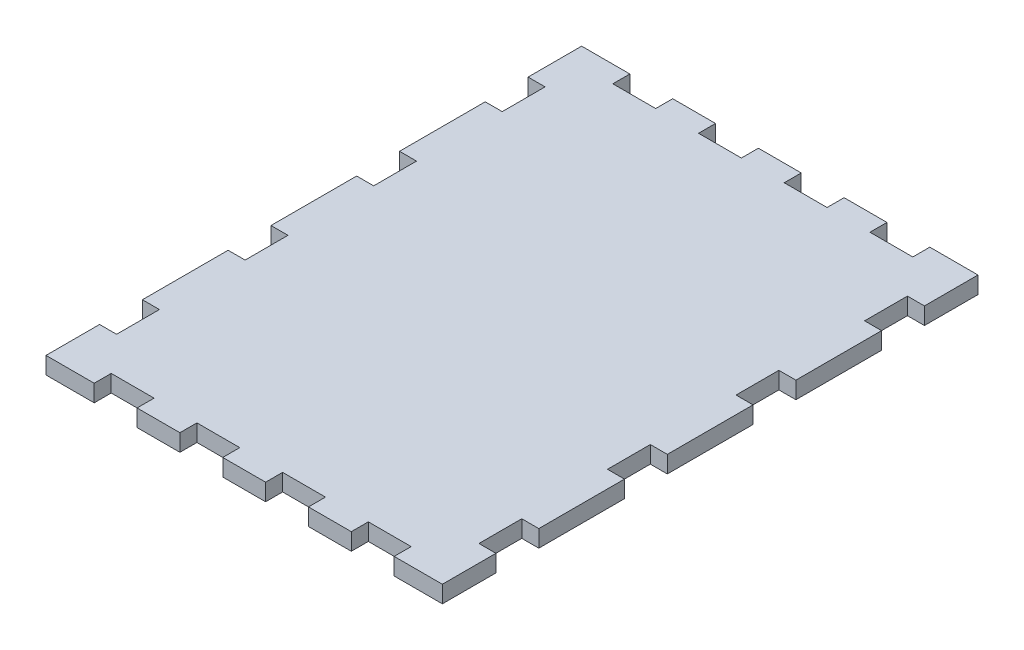
SolidWorks part; units mm, degrees
ref_plane "Front Plane" through (0, 0, 0) normal (0, 0, 1) x (1, 0, 0)
ref_plane "Top Plane" through (0, 0, 0) normal (0, 1, 0) x (1, 0, 0)
ref_plane "Right Plane" through (0, 0, 0) normal (1, 0, 0) x (0, 0, -1)
sketch "Sketch1" plane through (0, 0, 0) normal (0, 1, 0) x (1, 0, 0)
  line L1 (0, 0) -> (74, 0)
  line L2 (0, 0) -> (0, -100)
  line L3 (0, -100) -> (74, -100)
  line L4 (74, 0) -> (74, -100)
  dimension "D1" = 100
  dimension "D2" = 74
extrude "Boss-Extrude1" add sketch "Sketch1" along normal blind 3.175
sketch "Sketch2" plane through (0, 3.175, 0) normal (0, 1, 0) x (1, 0, 0)
  line L0 (37, 0) -> (37, -100) construction
  line L1 (74, 0) -> (0, 0) construction
  line L2 (0, -100) -> (74, -100) construction
  line L3 (57, 0) -> (57, -3.175)
  line L4 (41, 0) -> (49, 0)
  line L5 (41, 0) -> (41, -3.175)
  line L6 (41, -3.175) -> (49, -3.175)
  line L7 (49, 0) -> (49, -3.175)
  line L8 (57, 0) -> (65, 0)
  line L9 (57, -3.175) -> (65, -3.175)
  line L10 (65, 0) -> (65, -3.175)
  line L11 (9, 0) -> (9, -3.175)
  line L12 (17, -3.175) -> (9, -3.175)
  line L13 (17, 0) -> (9, 0)
  line L14 (25, 0) -> (25, -3.175)
  line L15 (33, -3.175) -> (25, -3.175)
  line L16 (33, 0) -> (33, -3.175)
  line L17 (33, 0) -> (25, 0)
  line L18 (17, 0) -> (17, -3.175)
  line L19 (74, -50) -> (0, -50) construction
  line L20 (74, -100) -> (74, 0) construction
  line L21 (0, 0) -> (0, -100) construction
  line L22 (0, -18) -> (3.175, -18)
  line L23 (0, -42) -> (3.175, -42)
  line L24 (0, -42) -> (0, -34)
  line L25 (0, -34) -> (3.175, -34)
  line L26 (3.175, -42) -> (3.175, -34)
  line L27 (0, -18) -> (0, -10)
  line L28 (0, -10) -> (3.175, -10)
  line L29 (3.175, -18) -> (3.175, -10)
  line L30 (3.175, -82) -> (3.175, -90)
  line L31 (0, -90) -> (3.175, -90)
  line L32 (0, -82) -> (0, -90)
  line L33 (3.175, -58) -> (3.175, -66)
  line L34 (0, -66) -> (3.175, -66)
  line L35 (0, -58) -> (0, -66)
  line L36 (0, -58) -> (3.175, -58)
  line L37 (0, -82) -> (3.175, -82)
  line L38 (17, -100) -> (17, -96.825)
  line L39 (33, -100) -> (25, -100)
  line L40 (33, -100) -> (33, -96.825)
  line L41 (33, -96.825) -> (25, -96.825)
  line L42 (25, -100) -> (25, -96.825)
  line L43 (17, -100) -> (9, -100)
  line L44 (17, -96.825) -> (9, -96.825)
  line L45 (9, -100) -> (9, -96.825)
  line L46 (65, -100) -> (65, -96.825)
  line L47 (57, -96.825) -> (65, -96.825)
  line L48 (57, -100) -> (65, -100)
  line L49 (49, -100) -> (49, -96.825)
  line L50 (41, -96.825) -> (49, -96.825)
  line L51 (41, -100) -> (41, -96.825)
  line L52 (41, -100) -> (49, -100)
  line L53 (57, -100) -> (57, -96.825)
  line L54 (74, -82) -> (70.825, -82)
  line L55 (74, -58) -> (70.825, -58)
  line L56 (74, -58) -> (74, -66)
  line L57 (74, -66) -> (70.825, -66)
  line L58 (70.825, -58) -> (70.825, -66)
  line L59 (74, -82) -> (74, -90)
  line L60 (74, -90) -> (70.825, -90)
  line L61 (70.825, -82) -> (70.825, -90)
  line L62 (70.825, -18) -> (70.825, -10)
  line L63 (74, -10) -> (70.825, -10)
  line L64 (74, -18) -> (74, -10)
  line L65 (70.825, -42) -> (70.825, -34)
  line L66 (74, -34) -> (70.825, -34)
  line L67 (74, -42) -> (74, -34)
  line L68 (74, -42) -> (70.825, -42)
  line L69 (74, -18) -> (70.825, -18)
  dimension "D1" = 8
  dimension "D2" = 4
  dimension "D4" = 3.175
  dimension "D5" = 3.175
  dimension "D6" = 8
  dimension "D7" = 8
  dimension "D3" = 2
  dimension "D8" = 2
extrude "Cut-Extrude1" cut sketch "Sketch2" against normal up to next
